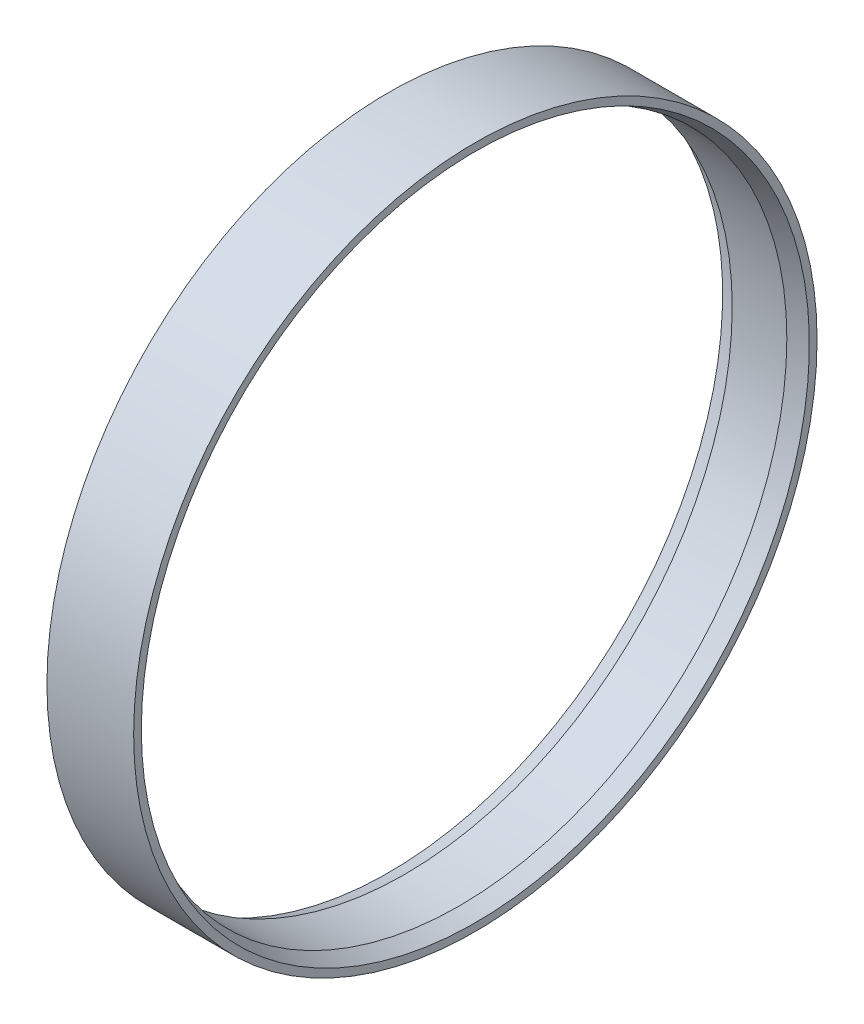
SolidWorks part; units mm, degrees
ref_plane "Płaszczyzna przednia" through (0, 0, 0) normal (0, 0, 1) x (1, 0, 0)
ref_plane "Płaszczyzna górna" through (0, 0, 0) normal (0, 1, 0) x (1, 0, 0)
ref_plane "Płaszczyzna prawa" through (0, 0, 0) normal (1, 0, 0) x (0, 0, -1)
sketch "Szkic2" plane through (0, 0, 0) normal (0, 0, 1) x (1, 0, 0)
  line L2 (-4.7505, -0.9002) -> (4.7495, -0.9002)
  line L6 (4.7495, -0.9002) -> (6.7571, -0.0972)
  line L9 (-4.7505, -0.9002) -> (-6.7429, -0.1002)
  line L12 (-6.7429, -0.1002) -> (-6.7429, 1.2998)
  line L13 (-6.7429, 1.2998) -> (6.7571, 1.2998)
  line L14 (6.7571, 1.2998) -> (6.7571, -0.0972)
  line L15 (-6.7429, 0.0998) -> (-4.2524, -0.9002)
  line L16 (6.7571, 0.1028) -> (4.2495, -0.9002)
  line L18 (-9.7184, -51.9002) -> (10.2174, -51.9002) construction
  point P5 (0, 0)
  point P18 (0.2495, -51.9002)
  dimension "D1" = 13.5
  dimension "D2" = 9.5
  dimension "D3" = 0.8
  dimension "D4" = 1.4
  dimension "D5" = 0.2
  dimension "D6" = 0.2
  dimension "D7" = 51
revolve "Obrót1" add sketch "Szkic2" angle 360 about L18 region at (0.0047, 0.2703, 0)
